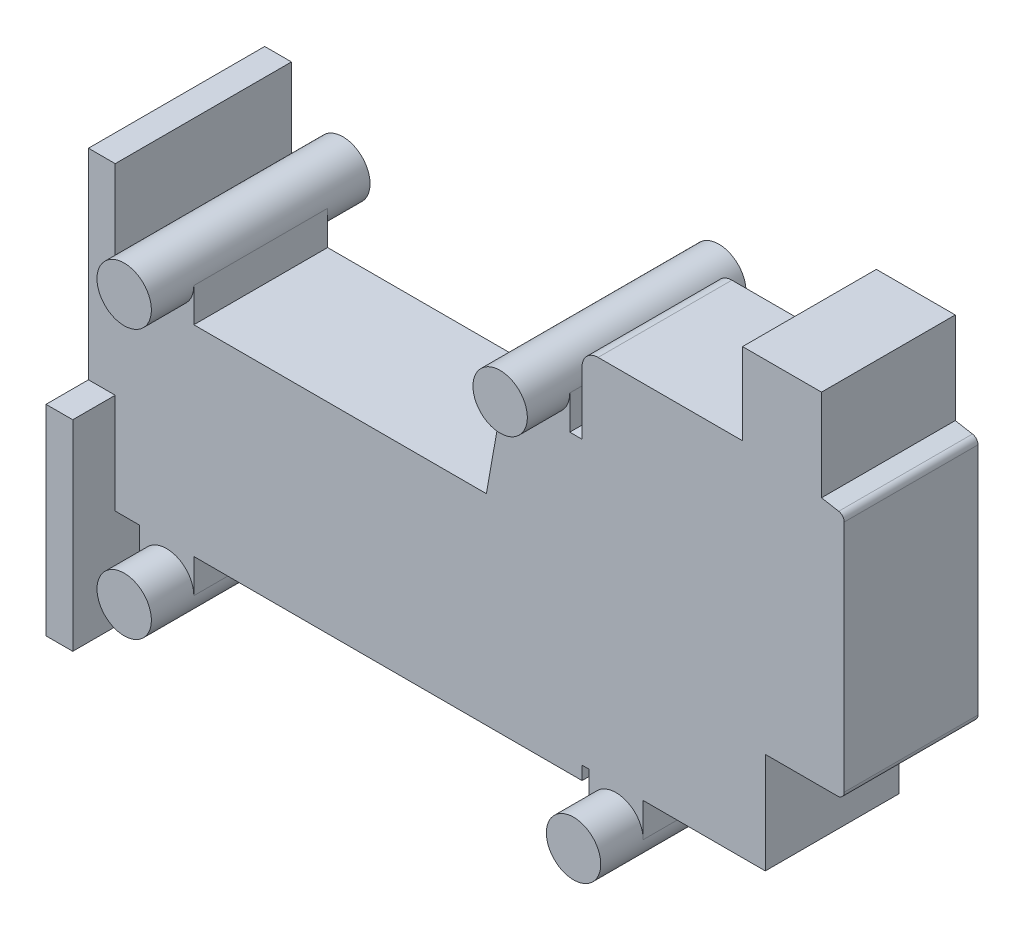
SolidWorks part; units mm, degrees
ref_plane "Front Plane" through (0, 0, 0) normal (0, 0, 1) x (1, 0, 0)
ref_plane "Top Plane" through (0, 0, 0) normal (0, 1, 0) x (1, 0, 0)
ref_plane "Right Plane" through (0, 0, 0) normal (1, 0, 0) x (0, 0, -1)
sketch "Sketch1" plane through (0, 0, 0) normal (0, 0, 1) x (1, 0, 0)
  line L1 (-12.7, 7.5) -> (12.7, 7.5)
  line L2 (-12.7, 7.5) -> (-12.7, -7.5)
  line L3 (-12.7, -7.5) -> (12.7, -7.5)
  line L4 (12.7, 7.5) -> (12.7, -7.5)
  line L5 (-12.7, 7.5) -> (12.7, -7.5) construction
  line L6 (-12.7, -7.5) -> (12.7, 7.5) construction
  point P0 (0, 0)
  dimension "D1" = 25.4
  dimension "D2" = 15
extrude "Boss-Extrude1" add sketch "Sketch1" along normal blind 10
sketch "Sketch2" plane through (0, 0, 10) normal (0, 0, 1) x (1, 0, 0)
  line L0 (35.9, 20.5) -> (40.97, 19.606) construction
  line L1 (41.3868, 19.5325) -> (40.97, 19.606) construction
  line L2 (41.8, 1.55) -> (41.8, 19.0401) construction
  line L3 (40.1, 19.7594) -> (40.1, 26.6) construction
  line L4 (40.1, 26.6) -> (34.2, 26.6) construction
  line L5 (34.2, 26.6) -> (34.2, 20.5) construction
  line L6 (23.4, 20.5) -> (34.7, 20.5) construction
  line L7 (22.2, 3.5) -> (22.2, 19.3) construction
  line L8 (16.3, 14.6) -> (22.2, 14.6) construction
  line L9 (16.3, 14.6) -> (15.048, 7.5) construction
  line L10 (9.4, 7.5) -> (15.048, 7.5) construction
  line L11 (40.1, 19.7594) -> (40.97, 19.606)
  line L12 (41.3868, 19.5325) -> (40.97, 19.606)
  line L13 (41.8, 1.55) -> (41.8, 19.0401)
  line L14 (40.1, 19.7594) -> (40.1, 26.6)
  line L15 (40.1, 26.6) -> (34.2, 26.6)
  line L16 (34.2, 26.6) -> (34.2, 20.5)
  line L17 (23.4, 20.5) -> (34.2, 20.5)
  line L18 (22.2, 14.6) -> (22.2, 19.3)
  line L19 (16.3, 14.6) -> (22.2, 14.6)
  line L20 (16.3, 14.6) -> (15.048, 7.5)
  line L21 (9.4, 7.5) -> (15.048, 7.5)
  line L22 (40.8832, 1.05) -> (35.9, 1.05) construction
  line L23 (40.8832, 1.05) -> (41.3, 1.05) construction
  line L24 (40.8832, 1.05) -> (35.9, 1.05)
  line L25 (40.8832, 1.05) -> (41.3, 1.05)
  line L26 (35.9, -2.35) -> (35.9, 1.05) construction
  line L27 (35.9, -2.35) -> (35.9, 1.05)
  line L28 (9.4, -7.5) -> (22.2, -7.5) construction
  line L29 (22.2, 14.6) -> (22.2, -7.5) construction
  line L30 (35.9, -2.35) -> (35.9, -6.5) construction
  line L31 (34.9, -6.5) -> (35.9, -6.5) construction
  line L32 (34.9, -6.5) -> (22.2, -6.5) construction
  line L33 (9.4, -7.5) -> (22.2, -7.5)
  line L34 (22.2, -6.5) -> (22.2, -7.5)
  line L35 (35.9, -2.35) -> (35.9, -6.5)
  line L36 (34.9, -6.5) -> (35.9, -6.5)
  line L37 (34.9, -6.5) -> (22.2, -6.5)
  line L38 (9.4, -7.5) -> (9.4, 7.5)
  line L41 (-12.7, 11) -> (-12.7, 14.2) construction
  line L42 (-12.7, 7.5) -> (-12.7, 12.7105) construction
  line L43 (-14.7, 14.2) -> (-14.7, 14.9937)
  line L44 (-12.7, -14.2) -> (-12.7, -10.0691) construction
  line L45 (-14.7, -10.0691) -> (-14.7, -14.2) construction
  line L46 (-14.7, -10.0691) -> (-14.7, 0) construction
  line L47 (-14.7, 0) -> (-14.7, 7.5) construction
  line L48 (-14.7, 7.5) -> (-14.7, 12.7105) construction
  line L49 (-14.7, 14.2) -> (-14.7, 11) construction
  line L50 (-12.7, 12.7105) -> (-12.7, 14.2)
  line L51 (-12.7, 7.5) -> (-12.7, 12.7105)
  line L52 (-12.7, 0) -> (-12.7, 7.5)
  line L53 (-12.7, -14.2) -> (-12.7, -10.0691)
  line L54 (-14.7, -10.0691) -> (-14.7, -14.2)
  line L55 (-14.7, -10.0691) -> (-14.7, 0)
  line L56 (-14.7, 0) -> (-14.7, 7.5)
  line L57 (-14.7, 7.5) -> (-14.7, 11)
  line L58 (-14.7, 14.2) -> (-14.7, 11)
  line L59 (-12.7, -10.0691) -> (-12.7, 0) construction
  line L61 (-12.7, -10.0691) -> (-12.7, 0)
  line L63 (-14.7, 14.9937) -> (-12.7, 14.9937)
  line L64 (-12.7, 14.9937) -> (-12.7, 14.2)
  line L65 (-14.7, -14.2) -> (-14.7, -14.9938)
  line L66 (-14.7, -14.9938) -> (-12.7, -14.9938)
  line L67 (-12.7, -14.9938) -> (-12.7, -14.2)
  arc A0 (41.8, 19.0401) -> (41.3868, 19.5325) centre (41.3, 19.0401) ccw construction
  arc A1 (23.4, 20.5) -> (22.2, 19.3) centre (23.4, 19.3) ccw construction
  arc A2 (41.8, 19.0401) -> (41.3868, 19.5325) centre (41.3, 19.0401) ccw
  arc A3 (23.4, 20.5) -> (22.2, 19.3) centre (23.4, 19.3) ccw
  arc A4 (41.3, 1.05) -> (41.8, 1.55) centre (41.3, 1.55) ccw construction
  arc A5 (41.3, 1.05) -> (41.8, 1.55) centre (41.3, 1.55) ccw
  dimension "D1" = 0.7937
extrude "Boss-Extrude2" add sketch "Sketch2" against normal up to surface (10 mm away) up to face at (0, 0, 0)
sketch "Sketch3" plane through (-14.7, 0, 0) normal (-1, 0, 0) x (0, 0, 1)
  line L0 (0, 14.9937) -> (-3.175, 14.9937)
  line L1 (-3.175, 14.9937) -> (-3.175, 0)
  line L2 (-3.175, 0) -> (0, 0)
  line L3 (0, -14.9938) -> (0, 14.9937) construction
  line L4 (0, 0) -> (0, 14.9937)
  line L5 (10, 14.9937) -> (10, -14.9938) construction
  line L6 (10, 0) -> (13.175, 0)
  line L7 (10, 0) -> (10, -14.9938)
  line L8 (10, -14.9938) -> (13.175, -14.9938)
  line L9 (13.175, 0) -> (13.175, -14.9938)
  dimension "D1" = 3.175
extrude "Boss-Extrude3" add sketch "Sketch3" against normal up to surface (2 mm away) up to face at (-12.7, 11.2469, 5)
sketch "Sketch4" plane through (0, 0, 10) normal (0, 0, 1) x (1, 0, 0)
  line L0 (9.61, 7.5) -> (15.048, 7.5) construction
  line L1 (15.048, 7.5) -> (-12.7, 7.5) construction
  line L2 (9.61, 7.5) -> (9.61, 12.2625) construction
  line L3 (12.329, 7.5) -> (12.329, 10.04) construction
  line L4 (10.297, 7.5) -> (10.297, 10.04)
  line L5 (14.361, 7.5) -> (14.361, 10.04)
  line L6 (0, 0) -> (35.9, 0) construction
  line L7 (35.9, -6.5) -> (35.9, 1.05) construction
  line L8 (9.61, -7.5) -> (15.048, -7.5) construction
  line L9 (12.329, -7.5) -> (12.329, -10.04) construction
  line L10 (10.297, -7.5) -> (10.297, -10.04)
  line L11 (14.361, -7.5) -> (14.361, -10.04)
  arc A0 (10.297, 7.5) -> (14.361, 7.5) centre (12.329, 7.5) ccw
  arc A1 (14.361, 10.04) -> (10.297, 10.04) centre (12.329, 10.04) ccw
  arc A2 (10.297, -7.5) -> (14.361, -7.5) centre (12.329, -7.5) cw
  arc A3 (14.361, -10.04) -> (10.297, -10.04) centre (12.329, -10.04) cw
  point P9 (12.329, 8.77)
  point P23 (12.329, -8.77)
  dimension "D1" = 2.032
  dimension "D2" = 2.54
extrude "Boss-Extrude4" [suppressed] add sketch "Sketch4" against normal up to surface (10 mm away)
sketch "Sketch5" [suppressed] plane through (0, 0, 0) normal (0, 0, -1) x (-1, 0, 0)
  circle A0 centre (-12.329, 10.04) radius 2.032
  circle A1 centre (-12.329, -10.04) radius 2.032
  arc A2 (-14.361, -10.04) -> (-10.297, -10.04) centre (-12.329, -10.04) ccw construction
  arc A3 (-10.297, 10.04) -> (-14.361, 10.04) centre (-12.329, 10.04) ccw construction
extrude "Boss-Extrude5" [suppressed] add sketch "Sketch5" along normal blind 3.175 and the other way blind 13.175
sketch "Sketch6" plane through (0, 0, 10) normal (0, 0, 1) x (1, 0, 0)
  line L0 (-5.01, 7.5) -> (-12.7, 7.5) construction
  line L1 (-5.01, 12.2625) -> (-5.01, 7.5) construction
  line L2 (10.297, 7.5) -> (-12.7, 7.5) construction
  line L3 (-8.855, 7.5) -> (-8.855, 10.04) construction
  line L4 (-10.887, 7.5) -> (-10.887, 10.04)
  line L5 (-6.823, 7.5) -> (-6.823, 10.04)
  line L6 (-12.7, 0) -> (0, 0) construction
  line L7 (-8.855, -7.5) -> (-8.855, -10.04) construction
  line L8 (-10.887, -7.5) -> (-10.887, -10.04)
  line L9 (-6.823, -7.5) -> (-6.823, -10.04)
  line L10 (19.25, 14.6) -> (19.25, 17.14) construction
  line L14 (22.2, 14.6) -> (16.3, 14.6) construction
  line L18 (17.218, 14.6) -> (17.218, 17.14)
  line L19 (21.282, 14.6) -> (21.282, 17.14)
  line L20 (22.2, -6.5) -> (27.28, -6.5) construction
  line L21 (22.2, -6.5) -> (35.9, -6.5) construction
  line L22 (24.74, -6.5) -> (24.74, -9.04) construction
  line L23 (26.772, -6.5) -> (26.772, -9.04)
  line L24 (22.708, -6.5) -> (22.708, -9.04)
  arc A0 (-10.887, 7.5) -> (-6.823, 7.5) centre (-8.855, 7.5) ccw
  arc A1 (-6.823, 10.04) -> (-10.887, 10.04) centre (-8.855, 10.04) ccw
  arc A2 (-10.887, -7.5) -> (-6.823, -7.5) centre (-8.855, -7.5) cw
  arc A3 (-6.823, -10.04) -> (-10.887, -10.04) centre (-8.855, -10.04) cw
  arc A10 (17.218, 14.6) -> (21.282, 14.6) centre (19.25, 14.6) ccw
  arc A11 (21.282, 17.14) -> (17.218, 17.14) centre (19.25, 17.14) ccw
  arc A12 (26.772, -6.5) -> (22.708, -6.5) centre (24.74, -6.5) ccw
  arc A13 (22.708, -9.04) -> (26.772, -9.04) centre (24.74, -9.04) ccw
  point P9 (-8.855, 8.77)
  point P20 (-8.855, -8.77)
  point P29 (19.25, 15.87)
  point P40 (24.74, -7.77)
  dimension "D1" = 2.032
  dimension "D4" = 2.032
  dimension "D2" = 2.54
  dimension "D3" = 2.54
  dimension "D5" = 5.08
extrude "Boss-Extrude6" add sketch "Sketch6" against normal up to surface (10 mm away) up to face at (19.5643, 7.0398, 0)
sketch "Sketch7" plane through (0, 0, 0) normal (0, 0, -1) x (-1, 0, 0)
  circle A0 centre (-19.25, 17.14) radius 2.032
  circle A1 centre (-24.74, -9.04) radius 2.032
  circle A2 centre (8.855, -10.04) radius 2.032
  circle A3 centre (8.855, 10.04) radius 2.032
extrude "Boss-Extrude7" add sketch "Sketch7" along normal blind 3.175 and the other way blind 13.175
sketch "Sketch8" [suppressed] plane through (0, 14.9937, 0) normal (0, 1, 0) x (1, 0, 0)
  line L0 (-12.7, -13.175) -> (-14.7, -13.175) construction
  line L1 (-12.7, 0) -> (-14.7, 0)
  line L2 (-12.7, 0) -> (-12.7, 3.175)
  line L3 (-12.7, 3.175) -> (-14.7, 3.175)
  line L4 (-14.7, 0) -> (-14.7, 3.175)
  line L5 (-12.7, -10) -> (-14.7, -10)
  line L6 (-12.7, -10) -> (-12.7, -13.175)
  line L7 (-12.7, -13.175) -> (-14.7, -13.175)
  line L8 (-14.7, -10) -> (-14.7, -13.175)
extrude "Cut-Extrude1" [suppressed] cut sketch "Sketch8" against normal through all
